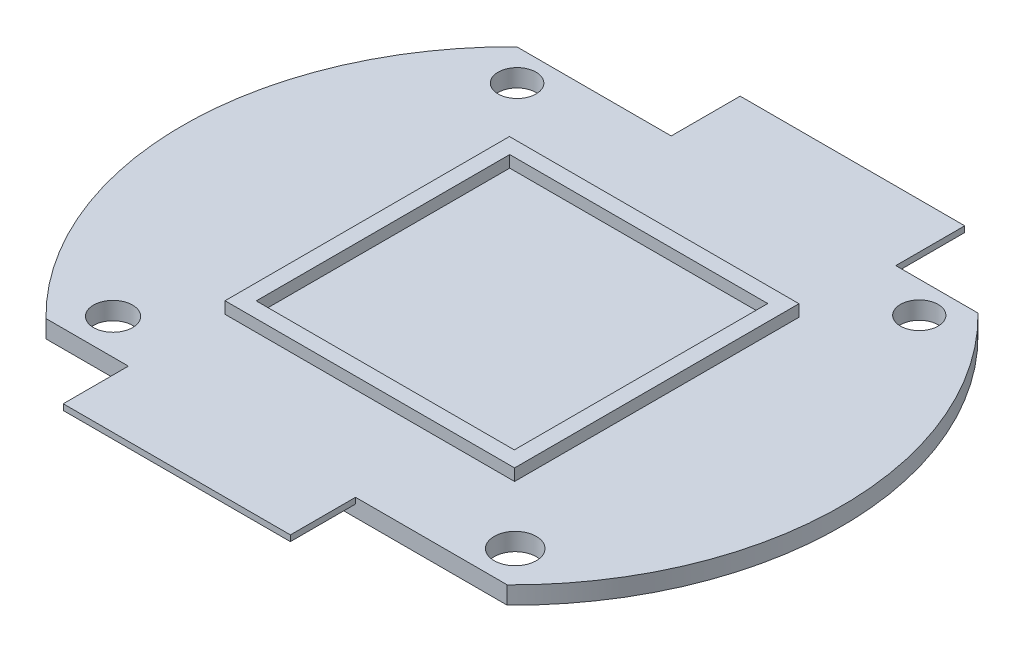
SolidWorks part; units mm, degrees
ref_plane "Front" through (0, 0, 0) normal (0, 0, 1) x (1, 0, 0)
ref_plane "Top" through (0, 0, 0) normal (0, 1, 0) x (1, 0, 0)
ref_plane "Right" through (0, 0, 0) normal (1, 0, 0) x (0, 0, -1)
sketch "Sketch2" plane through (0, 0, 0) normal (0, 1, 0) x (1, 0, 0)
  line L0 (222.8698, 383.9763) -> (1148.2031, 383.9763) construction
  line L1 (0, 0) -> (56, 0) construction
  line L2 (8.4041, 20) -> (47.5959, 20)
  line L3 (8.4041, -20) -> (47.5959, -20)
  arc A0 (8.4041, 20) -> (8.4041, -20) centre (28, 0) ccw
  arc A1 (47.5959, -20) -> (47.5959, 20) centre (28, 0) ccw
  circle A2 centre (11.0877, 17.343) radius 1.6101
  circle A3 centre (11.0877, -16.9875) radius 1.6603
  circle A4 centre (45.2626, -16.9875) radius 1.7912
  circle A5 centre (45.2626, 17.343) radius 1.6009
  dimension "D2" = 56
  dimension "D1" = 56
  dimension "D3" = 40
extrude "Boss-Extrude1" add sketch "Sketch2" along normal blind 1.5
sketch "Sketch3" plane through (0, 1.5, 0) normal (0, 1, 0) x (1, 0, 0)
  line L0 (47.5959, 20) -> (8.4041, 20) construction
  line L1 (21.5286, 20) -> (40.6098, 20)
  line L2 (21.5286, 20) -> (21.5286, 25.8586)
  line L3 (21.5286, 25.8586) -> (40.6098, 25.8586)
  line L4 (40.6098, 20) -> (40.6098, 25.8586)
  line L5 (8.4041, -20) -> (47.5959, -20) construction
  line L6 (34.705, -20) -> (15.4051, -20)
  line L7 (34.705, -20) -> (34.705, -25.5349)
  line L8 (34.705, -25.5349) -> (15.4051, -25.5349)
  line L9 (15.4051, -20) -> (15.4051, -25.5349)
extrude "Boss-Extrude2" add sketch "Sketch3" against normal blind 0.5
sketch "Sketch4" plane through (0, 1.5, 0) normal (0, 1, 0) x (1, 0, 0)
  line L0 (0, 0) -> (56, 0) construction
  line L1 (15.699, 12.0829) -> (40.301, 12.0829)
  line L2 (15.699, 12.0829) -> (15.699, -12.0829)
  line L3 (15.699, -12.0829) -> (40.301, -12.0829)
  line L4 (40.301, 12.0829) -> (40.301, -12.0829)
  line L5 (15.699, 12.0829) -> (40.301, -12.0829) construction
  line L6 (15.699, -12.0829) -> (40.301, 12.0829) construction
  line L8 (17.0365, 10.7691) -> (38.9635, 10.7691)
  line L9 (17.0365, 10.7691) -> (17.0365, -10.7691)
  line L10 (17.0365, -10.7691) -> (38.9635, -10.7691)
  line L11 (38.9635, 10.7691) -> (38.9635, -10.7691)
  line L12 (17.0365, 10.7691) -> (38.9635, -10.7691) construction
  line L13 (17.0365, -10.7691) -> (38.9635, 10.7691) construction
  point P0 (28, 0)
  point P7 (28, 0)
extrude "Boss-Extrude3" add sketch "Sketch4" along normal blind 1
